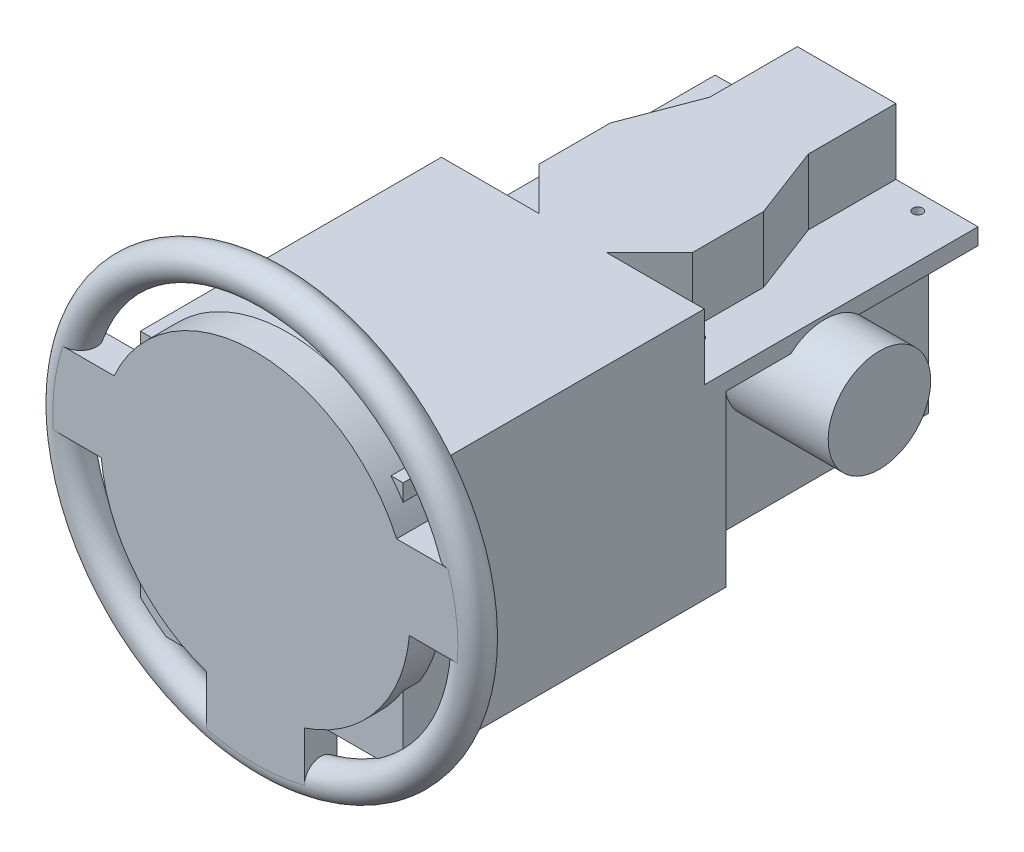
SolidWorks part; units mm, degrees
ref_plane "Płaszczyzna przednia" through (0, 0, 0) normal (0, 0, 1) x (1, 0, 0)
ref_plane "Płaszczyzna górna" through (0, 0, 0) normal (0, 1, 0) x (1, 0, 0)
ref_plane "Płaszczyzna prawa" through (0, 0, 0) normal (1, 0, 0) x (0, 0, -1)
sketch "Szkic4" plane through (0, 0, 0) normal (0, 1, 0) x (1, 0, 0)
  line L0 (0, 0) -> (0, -14.1713) construction
  line L1 (0, 0) -> (-185, 0) construction
  circle A0 centre (-185, 0) radius 15
  dimension "D1" = 30
  dimension "D2" = 185
revolve "Obrót2" add sketch "Szkic4" angle 360 about L0
sketch "Szkic5" plane through (0, 0, 0) normal (0, 0, 1) x (1, 0, 0)
  line L0 (0, 141.2771) -> (0, -223.1934) construction
  line L1 (-175.7848, 57.6603) -> (-128.9748, 57.6603)
  line L2 (-184.5472, -12.936) -> (-140.6836, -12.936)
  line L3 (-44.7738, -133.9945) -> (-44.7738, -179.5002)
  line L4 (44.7738, -133.9945) -> (44.7738, -179.5002)
  line L5 (128.9748, 57.6603) -> (175.7848, 57.6603)
  line L6 (140.6836, -12.936) -> (184.5472, -12.936)
  line L7 (-170, 0) -> (-200, 0) construction
  arc A0 (-140.6836, -12.936) -> (-44.7738, -133.9945) centre (0, 0) ccw
  arc A1 (-175.7848, 57.6603) -> (-184.5472, -12.936) centre (0, 0) ccw
  arc A2 (44.7738, -133.9945) -> (140.6836, -12.936) centre (0, 0) ccw
  arc A3 (128.9748, 57.6603) -> (-128.9748, 57.6603) centre (0, 0) ccw
  arc A4 (-44.7738, -179.5002) -> (44.7738, -179.5002) centre (0, 0) ccw
  arc A5 (184.5472, -12.936) -> (175.7848, 57.6603) centre (0, 0) ccw
  circle A6 centre (0, 0) radius 170 construction
  circle A7 centre (0, 0) radius 200 construction
  circle A8 centre (0, 0) radius 185 construction
  point P23 (-185, 0)
extrude "Dodanie-wyciągnięcie1" add sketch "Szkic5" against normal blind 15 and the other way blind 15 separate body contours L3 A4 L4 A2 L6 A5 L5 A3 L1 A1 L2 A0
sketch "Szkic6" plane through (0, 0, 0) normal (0, 1, 0) x (1, 0, 0)
  line L0 (0, -15) -> (0, 525) construction
  line L3 (-185, -15) -> (185, -15) construction
  dimension "D1" = 540
sketch "Szkic7" plane through (0, 0, 0) normal (0, 0, 1) x (1, 0, 0)
  line L0 (120, 90) -> (-120, -140) construction
  line L1 (120, 90) -> (-120, 90)
  line L2 (120, 90) -> (120, -140)
  line L3 (120, -140) -> (-120, -140)
  line L4 (-120, 90) -> (-120, -140)
  line L5 (-120, 90) -> (120, -140) construction
  line L6 (0, -140) -> (0, 0) construction
  point P4 (0, 0)
  dimension "D1" = 240
  dimension "D2" = 230
  dimension "D3" = 140
extrude "Dodanie-wyciągnięcie2" add sketch "Szkic7" against normal up to vertex (525 mm away) up to point (0, 0, -525)
sketch "Szkic8" plane through (0, 0, 0) normal (0, 1, 0) x (1, 0, 0)
  line L0 (0, -15) -> (0, 445)
  line L1 (0, -15) -> (0, 525) construction
  dimension "D1" = 460
sketch "Szkic9" plane through (0, 0, -525) normal (0, 0, -1) x (-1, 0, 0)
  line L0 (120, -74.5601) -> (120, 74.5601) construction
  line L1 (-120, 90) -> (120, 90)
  line L2 (-120, 90) -> (-120, 30)
  line L3 (-120, 30) -> (120, 30)
  line L4 (120, 90) -> (120, 30)
  line L6 (-70, 30) -> (70, 30)
  line L7 (-70, 30) -> (-70, 90)
  line L8 (-70, 90) -> (70, 90)
  line L9 (70, 30) -> (70, 90)
  point P11 (0, 90)
  point P12 (0, 90)
  line M5 (-120, 90) -> (-120, -140)
  line M7 (120, -140) -> (120, 90)
  line M8 (120, 90) -> (-120, 90)
  dimension "D1" = 60
  dimension "D2" = 140
extrude "Wytnij-wyciągnięcie1" cut sketch "Szkic9" against normal blind 250 contours L3 L7 L1 M5 | L9 L3 M7 M8 region at (95, 60, -525) region at (-95, 60, -525)
sketch "Szkic10" plane through (0, 0, -525) normal (0, 0, -1) x (-1, 0, 0)
  line L0 (120, -140) -> (-120, -140) construction
  line L1 (-75, -140) -> (75, -140)
  line L2 (-75, -140) -> (-75, 15)
  line L3 (-75, 15) -> (75, 15)
  line L4 (75, -140) -> (75, 15)
  line L5 (120, 30) -> (120, -140) construction
  line L6 (-120, -140) -> (120, -140)
  line L7 (-120, -140) -> (-120, 15)
  line L8 (-120, 15) -> (120, 15)
  line L9 (120, -140) -> (120, 15)
  line L10 (-120, 30) -> (-70, 30) construction
  point P13 (0, 15)
  point P14 (0, 15)
  line M10 (-120, 30) -> (-120, -140)
  line M11 (-120, -140) -> (120, -140)
  line M12 (120, -140) -> (120, 30)
  dimension "D1" = 150
  dimension "D2" = 15
extrude "Wytnij-wyciągnięcie2" cut sketch "Szkic10" against normal blind 230 contours L8 L4 M11 M12 | L8 L2 M10 M11 region at (97.5, -62.5, -525) region at (-97.5, -62.5, -525)
sketch "Szkic11" plane through (0, 30, 0) normal (0, 1, 0) x (1, 0, 0)
  line L0 (120, 525) -> (70, 525) construction
  line L1 (0, -15) -> (0, 525) construction
  circle A0 centre (80, 510) radius 4.5
  circle A1 centre (80, 310) radius 4.5
  circle A2 centre (-80, 310) radius 4.5
  circle A3 centre (-80, 510) radius 4.5
  point P12 (80, 490.7332)
  point P13 (0, 0)
  point P14 (0, 0)
  point P15 (0, 0)
  dimension "D1" = 9
  dimension "D2" = 160
  dimension "D3" = 160
  dimension "D4" = 200
  dimension "D5" = 15
  dimension "D6" = 80
extrude "Wytnij-wyciągnięcie3" cut sketch "Szkic11" against normal blind 230
sketch "Szkic12" plane through (0, 0, -525) normal (0, 0, -1) x (-1, 0, 0)
  line L0 (75, -140) -> (75, 15) construction
  line L1 (-75, 15) -> (75, 15)
  line L2 (-75, 15) -> (-75, -25)
  line L3 (-75, -25) -> (75, -25)
  line L4 (75, 15) -> (75, -25)
  line L6 (-45, 15) -> (45, 15)
  line L7 (-45, 15) -> (-45, -25)
  line L8 (-45, -25) -> (45, -25)
  line L9 (45, 15) -> (45, -25)
  point P11 (0, -25)
  point P12 (0, -25)
  line M9 (75, -140) -> (75, 15)
  line M15 (-75, 15) -> (-75, -140)
  dimension "D1" = 90
  dimension "D2" = 40
extrude "Wytnij-wyciągnięcie4" cut sketch "Szkic12" against normal up to surface (230 mm away) contours L7 L1 L3 M15 | L1 L9 L3 M9 region at (60, -5, -525) region at (-60, -5, -525) up to face at (97.5, -62.5, -295)
sketch "Szkic13" plane through (120, 0, 0) normal (1, 0, 0) x (0, 0, -1)
  line L0 (525, -140) -> (525, -25) construction
  line L1 (275, 90) -> (0, 90) construction
  circle A0 centre (385, -20) radius 46.8123
  dimension "D1" = 140
  dimension "D2" = 110
extrude "Dodanie-wyciągnięcie3" add sketch "Szkic13" against normal up to surface (75 mm away) and the other way blind 50 up to face at (45, -5, -410)
sketch "Szkic14" plane through (0, 90, 0) normal (0, 1, 0) x (1, 0, 0)
  line L0 (70, 314.1421) -> (30.8579, 275)
  line L1 (70, 275) -> (70, 525) construction
  line L2 (30.8579, 275) -> (-30.8579, 275)
  line L3 (120, 275) -> (70, 275) construction
  line L4 (0, -15) -> (0, 525) construction
  line L5 (70, 379.1421) -> (45, 445)
  line L6 (70, 275) -> (70, 525) construction
  line L8 (70, 314.1421) -> (70, 379.1421)
  line L9 (45, 445) -> (45, 525)
  line L10 (70, 525) -> (-70, 525) construction
  line L11 (45, 525) -> (-45, 525)
  line L12 (0, -220) -> (0, 220) construction
  line L13 (-45, 445) -> (-45, 525)
  line L14 (-70, 379.1421) -> (-45, 445)
  line L15 (-70, 314.1421) -> (-70, 379.1421)
  line L16 (-70, 314.1421) -> (-30.8579, 275)
  line L18 (70, 275) -> (-70, 275)
  line L19 (70, 275) -> (70, 525)
  line L20 (70, 525) -> (-70, 525)
  line L21 (-70, 275) -> (-70, 525)
  circle A1 centre (80, 310) radius 4.5 construction
  point P23 (0, 525)
  point P27 (0, 275)
  line M11 (70, 275) -> (70, 525)
  line M12 (70, 525) -> (-70, 525)
  line M13 (-70, 525) -> (-70, 275)
  dimension "D1" = 10
  dimension "D2" = 45
  dimension "D3" = 80
  dimension "D4" = 45
  dimension "D5" = 65
extrude "Wytnij-wyciągnięcie5" cut sketch "Szkic14" against normal up to surface (60 mm away) contours L18 L0 M11 | L18 L16 M13 | L14 L13 M13 M12 | L9 L5 M11 M12 region at (56.9526, 90, -288.0474) region at (58.715, 90, -466.9352) region at (-56.9526, 90, -288.0474) region at (-58.715, 90, -466.9352) up to face at (80, 30, -305.5)
